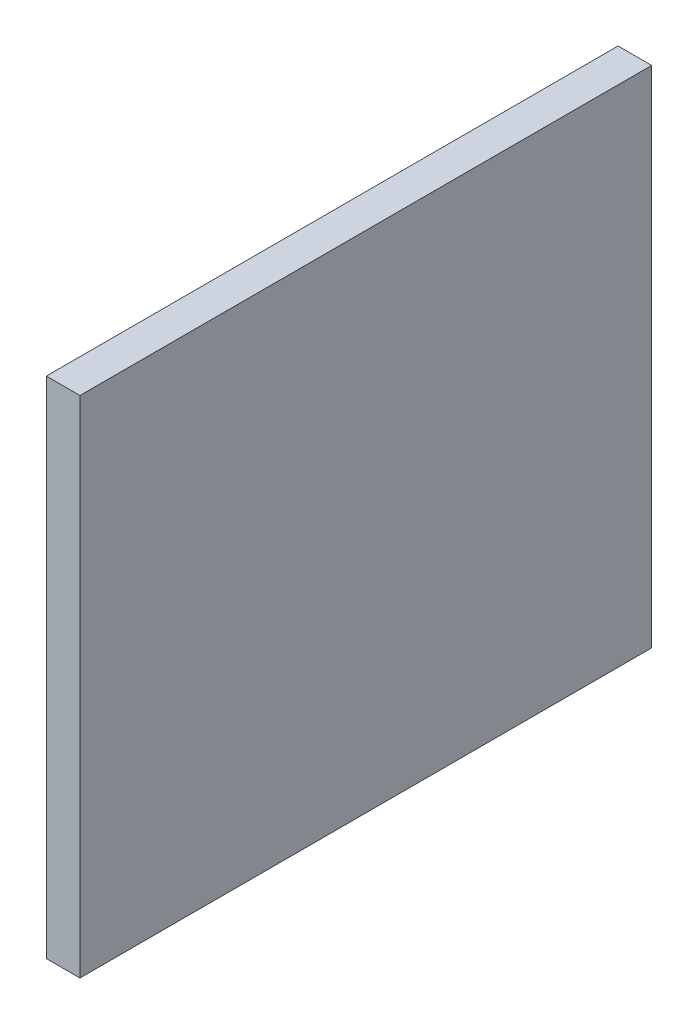
SolidWorks part; units mm, degrees
ref_plane "Front Plane" through (0, 0, 0) normal (0, 0, 1) x (1, 0, 0)
ref_plane "Top Plane" through (0, 0, 0) normal (0, 1, 0) x (1, 0, 0)
ref_plane "Right Plane" through (0, 0, 0) normal (1, 0, 0) x (0, 0, -1)
sketch "Sketch1" plane through (0, 0, 0) normal (0, 0, 1) x (1, 0, 0)
  line L0 (0, 0) -> (0, -150) construction
  line L1 (0, -150) -> (150, -150) construction
  line L2 (150, -150) -> (150, 0) construction
  line L3 (150, -150) -> (150, 0)
  line L4 (150, 0) -> (160, 0)
  line L5 (160, 0) -> (160, -150)
  line L6 (160, -150) -> (150, -150)
  circle A0 centre (0, 0) radius 150 construction
  dimension "D1" = 300
  dimension "D2" = 10
extrude "Boss-Extrude1" add sketch "Sketch1" along normal blind 170
